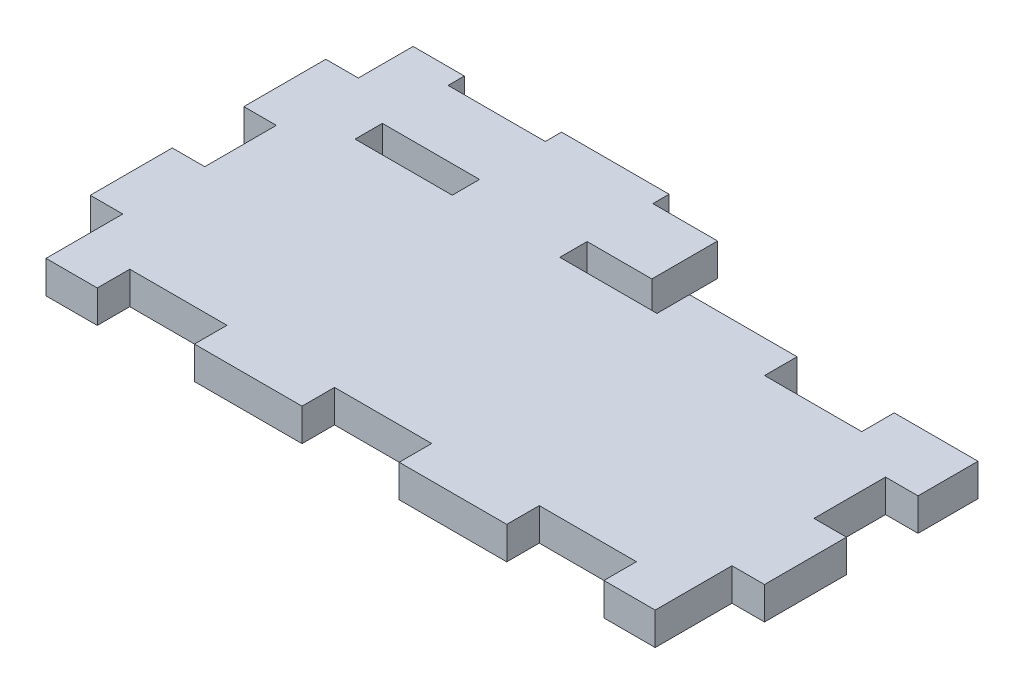
SolidWorks part; units mm, degrees
ref_plane "Front Plane" through (0, 0, 0) normal (0, 0, 1) x (1, 0, 0)
ref_plane "Top Plane" through (0, 0, 0) normal (0, 1, 0) x (1, 0, 0)
ref_plane "Right Plane" through (0, 0, 0) normal (1, 0, 0) x (0, 0, -1)
sketch "Sketch1" plane through (0, 0, 0) normal (0, 1, 0) x (1, 0, 0)
  line L1 (0, 0) -> (65.35, 0)
  line L2 (0, 0) -> (0, 35.35)
  line L3 (0, 35.35) -> (65.35, 35.35)
  line L4 (65.35, 0) -> (65.35, 35.35)
  dimension "D1" = 65.35
  dimension "D2" = 35.35
extrude "Boss-Extrude1" add sketch "Sketch1" along normal blind 3.175
sketch "Sketch2" plane through (0, 0, 0) normal (0, -1, 0) x (1, 0, 0)
  line L0 (65.35, -35.35) -> (0, -35.35) construction
  line L1 (65.35, -35.35) -> (37.175, -35.35)
  line L2 (65.35, -35.35) -> (65.35, -27.85)
  line L3 (65.35, -27.85) -> (37.175, -27.85)
  line L4 (37.175, -35.35) -> (37.175, -27.85)
  line L5 (65.35, 0) -> (65.35, -35.35) construction
  dimension "D1" = 7.5
  dimension "D2" = 28.175
extrude "Cut-Extrude1" cut sketch "Sketch2" against normal through all
sketch "Sketch3" plane through (0, 0, 0) normal (0, -1, 0) x (1, 0, 0)
  line L0 (0, 0) -> (65.35, 0) construction
  line L1 (62.175, -7.5) -> (65.35, -7.5)
  line L2 (62.175, -7.5) -> (62.175, 0)
  line L3 (62.175, 0) -> (65.35, 0)
  line L4 (65.35, -7.5) -> (65.35, 0)
  line L5 (0, -35.35) -> (0, 0) construction
  line L6 (57.675, -3.175) -> (47.675, -3.175)
  line L7 (57.675, -3.175) -> (57.675, 0)
  line L8 (57.675, 0) -> (47.675, 0)
  line L9 (47.675, -3.175) -> (47.675, 0)
  line L10 (37.675, -3.175) -> (27.675, -3.175)
  line L11 (37.675, -3.175) -> (37.675, 0)
  line L12 (37.675, 0) -> (27.675, 0)
  line L13 (27.675, -3.175) -> (27.675, 0)
  line L14 (17.675, -3.175) -> (7.675, -3.175)
  line L15 (17.675, -3.175) -> (17.675, 0)
  line L16 (17.675, 0) -> (7.675, 0)
  line L17 (7.675, -3.175) -> (7.675, 0)
  line L18 (3.175, -7.5) -> (0, -7.5)
  line L19 (3.175, -7.5) -> (3.175, 0)
  line L20 (3.175, 0) -> (0, 0)
  line L21 (0, -7.5) -> (0, 0)
  line L22 (37.175, -35.35) -> (0, -35.35) construction
  line L23 (3.175, -15) -> (0, -15)
  line L24 (3.175, -15) -> (3.175, -22.5)
  line L25 (3.175, -22.5) -> (0, -22.5)
  line L26 (0, -15) -> (0, -22.5)
  line L27 (3.175, -30) -> (0, -30)
  line L28 (3.175, -30) -> (3.175, -35.35)
  line L29 (3.175, -35.35) -> (0, -35.35)
  line L30 (0, -30) -> (0, -35.35)
  line L31 (7.675, -33.7625) -> (17.675, -33.7625)
  line L32 (7.675, -33.7625) -> (7.675, -35.35)
  line L33 (7.675, -35.35) -> (17.675, -35.35)
  line L34 (17.675, -33.7625) -> (17.675, -35.35)
  line L35 (65.35, -27.85) -> (37.175, -27.85) construction
  line L36 (17.675, -27.85) -> (7.675, -27.85)
  line L37 (17.675, -27.85) -> (17.675, -24.675)
  line L38 (17.675, -24.675) -> (7.675, -24.675)
  line L39 (7.675, -27.85) -> (7.675, -24.675)
  line L40 (27.675, -27.85) -> (37.675, -27.85)
  line L41 (27.675, -27.85) -> (27.675, -24.675)
  line L42 (27.675, -24.675) -> (37.675, -24.675)
  line L43 (37.675, -27.85) -> (37.675, -24.675)
  line L44 (34, -27.85) -> (37.175, -27.85)
  line L45 (34, -27.85) -> (34, -33.7625)
  line L46 (34, -33.7625) -> (37.175, -33.7625)
  line L47 (37.175, -27.85) -> (37.175, -33.7625)
  line L48 (27.675, -33.7625) -> (37.175, -33.7625)
  line L49 (27.675, -33.7625) -> (27.675, -35.35)
  line L50 (27.675, -35.35) -> (37.175, -35.35)
  line L51 (37.175, -33.7625) -> (37.175, -35.35)
  line L52 (47.675, -24.675) -> (57.675, -24.675)
  line L53 (47.675, -24.675) -> (47.675, -27.85)
  line L54 (47.675, -27.85) -> (57.675, -27.85)
  line L55 (57.675, -24.675) -> (57.675, -27.85)
  line L56 (65.35, 0) -> (65.35, -27.85) construction
  line L57 (62.175, -22.5) -> (65.35, -22.5)
  line L58 (62.175, -22.5) -> (62.175, -15)
  line L59 (62.175, -15) -> (65.35, -15)
  line L60 (65.35, -22.5) -> (65.35, -15)
  line L62 (37.175, -27.85) -> (37.175, -35.35) construction
  line M40 (37.175, -35.35) -> (37.175, -27.85)
  line M41 (37.175, -27.85) -> (65.35, -27.85)
  line M42 (65.35, -27.85) -> (65.35, 0)
  line M43 (65.35, 0) -> (0, 0)
  line M44 (0, 0) -> (0, -35.35)
  line M45 (0, -35.35) -> (37.175, -35.35)
  dimension "D1" = 10
  dimension "D2" = 10
  dimension "D3" = 10
  dimension "D4" = 10
  dimension "D5" = 10
  dimension "D6" = 4.5
  dimension "D7" = 3.175
  dimension "D8" = 7.5
  dimension "D9" = 7.5
  dimension "D10" = 5.35
  dimension "D11" = 7.5
  dimension "D12" = 7.5
  dimension "D13" = 5.9125
  dimension "D14" = 1.5875
extrude "Cut-Extrude2" cut sketch "Sketch3" against normal blind 3.175 contours L9 L6 L7 M43 | L2 L1 M42 M43 | L59 L58 L57 M42 | L55 L52 L53 M41 | L43 L42 L41 L40 M41 | L45 L46 L40 M40 | L48 L49 L46 M45 M40 | L39 L36 L37 L38 | L28 L27 M44 M45 | L25 L24 L23 M44 | L18 L19 M43 M44 | L17 L14 L15 M43 | L13 L10 L11 M43 | L33 L34 L31 L32 region at (63.7625, 0, -3.75) region at (63.7625, 0, -18.75) region at (52.675, 0, -1.5875) region at (32.675, 0, -1.5875) region at (52.675, 0, -26.2625) region at (12.675, 0, -1.5875) region at (32.675, 0, -26.2625) region at (35.5875, 0, -30.8063) region at (1.5875, 0, -3.75) region at (32.425, 0, -34.5563) region at (1.5875, 0, -18.75) region at (1.5875, 0, -32.675) region at (12.675, 0, -26.2625)
sketch "Sketch6" plane through (0, 3.175, 0) normal (0, 1, 0) x (1, 0, 0)
  line L60 (17.421, 27.596) -> (7.929, 27.596)
  line L61 (7.929, 27.596) -> (7.929, 24.929)
  line L62 (7.929, 24.929) -> (17.421, 24.929)
  line L63 (17.421, 24.929) -> (17.421, 27.596)
  line L64 (17.421, 27.596) -> (7.929, 27.596)
  line L65 (7.929, 27.596) -> (7.929, 24.929)
  line L66 (7.929, 24.929) -> (17.421, 24.929)
  line L67 (17.421, 24.929) -> (17.421, 27.596)
  line L92 (7.929, -0.254) -> (7.929, 2.921)
  line L93 (7.929, 2.921) -> (17.421, 2.921)
  line L94 (17.421, 2.921) -> (17.421, -0.254)
  line L95 (17.421, -0.254) -> (27.929, -0.254)
  line L96 (27.929, -0.254) -> (27.929, 2.921)
  line L97 (27.929, 2.921) -> (37.421, 2.921)
  line L98 (37.421, 2.921) -> (37.421, -0.254)
  line L99 (37.421, -0.254) -> (47.929, -0.254)
  line L100 (47.929, -0.254) -> (47.929, 2.921)
  line L101 (47.929, 2.921) -> (57.421, 2.921)
  line L102 (57.421, 2.921) -> (57.421, -0.254)
  line L103 (57.421, -0.254) -> (62.429, -0.254)
  line L104 (62.429, -0.254) -> (62.429, 7.246)
  line L105 (62.429, 7.246) -> (65.604, 7.246)
  line L106 (65.604, 7.246) -> (65.604, 15.254)
  line L107 (65.604, 15.254) -> (62.429, 15.254)
  line L108 (62.429, 15.254) -> (62.429, 22.246)
  line L109 (62.429, 22.246) -> (65.604, 22.246)
  line L110 (65.604, 22.246) -> (65.604, 28.104)
  line L111 (65.604, 28.104) -> (57.421, 28.104)
  line L112 (57.421, 28.104) -> (57.421, 24.929)
  line L113 (57.421, 24.929) -> (47.929, 24.929)
  line L114 (47.929, 24.929) -> (47.929, 28.104)
  line L115 (47.929, 28.104) -> (37.421, 28.104)
  line L116 (37.421, 28.104) -> (37.421, 24.929)
  line L117 (37.421, 24.929) -> (27.929, 24.929)
  line L118 (27.929, 24.929) -> (27.929, 27.596)
  line L119 (27.929, 27.596) -> (34.254, 27.596)
  line L120 (34.254, 27.596) -> (34.254, 34.0165)
  line L121 (34.254, 34.0165) -> (27.929, 34.0165)
  line L122 (27.929, 34.0165) -> (27.929, 35.604)
  line L123 (27.929, 35.604) -> (17.421, 35.604)
  line L124 (17.421, 35.604) -> (17.421, 34.0165)
  line L125 (17.421, 34.0165) -> (7.929, 34.0165)
  line L126 (7.929, 34.0165) -> (7.929, 35.604)
  line L127 (7.929, 35.604) -> (2.921, 35.604)
  line L128 (2.921, 35.604) -> (2.921, 30.254)
  line L129 (2.921, 30.254) -> (-0.254, 30.254)
  line L130 (-0.254, 30.254) -> (-0.254, 22.246)
  line L131 (-0.254, 22.246) -> (2.921, 22.246)
  line L132 (2.921, 22.246) -> (2.921, 15.254)
  line L133 (2.921, 15.254) -> (-0.254, 15.254)
  line L134 (-0.254, 15.254) -> (-0.254, 7.246)
  line L135 (-0.254, 7.246) -> (2.921, 7.246)
  line L136 (2.921, 7.246) -> (2.921, -0.254)
  line L137 (2.921, -0.254) -> (7.929, -0.254)
  line L138 (7.929, -0.254) -> (7.929, 2.921)
  line L139 (7.929, 2.921) -> (17.421, 2.921)
  line L140 (17.421, 2.921) -> (17.421, -0.254)
  line L141 (17.421, -0.254) -> (27.929, -0.254)
  line L142 (27.929, -0.254) -> (27.929, 2.921)
  line L143 (27.929, 2.921) -> (37.421, 2.921)
  line L144 (37.421, 2.921) -> (37.421, -0.254)
  line L145 (37.421, -0.254) -> (47.929, -0.254)
  line L146 (47.929, -0.254) -> (47.929, 2.921)
  line L147 (47.929, 2.921) -> (57.421, 2.921)
  line L148 (57.421, 2.921) -> (57.421, -0.254)
  line L149 (57.421, -0.254) -> (62.429, -0.254)
  line L150 (62.429, -0.254) -> (62.429, 7.246)
  line L151 (62.429, 7.246) -> (65.604, 7.246)
  line L152 (65.604, 7.246) -> (65.604, 15.254)
  line L153 (65.604, 15.254) -> (62.429, 15.254)
  line L154 (62.429, 15.254) -> (62.429, 22.246)
  line L155 (62.429, 22.246) -> (65.604, 22.246)
  line L156 (65.604, 22.246) -> (65.604, 28.104)
  line L157 (65.604, 28.104) -> (57.421, 28.104)
  line L158 (57.421, 28.104) -> (57.421, 24.929)
  line L159 (57.421, 24.929) -> (47.929, 24.929)
  line L160 (47.929, 24.929) -> (47.929, 28.104)
  line L161 (47.929, 28.104) -> (37.421, 28.104)
  line L162 (37.421, 28.104) -> (37.421, 24.929)
  line L163 (37.421, 24.929) -> (27.929, 24.929)
  line L164 (27.929, 24.929) -> (27.929, 27.596)
  line L165 (27.929, 27.596) -> (34.254, 27.596)
  line L166 (34.254, 27.596) -> (34.254, 34.0165)
  line L167 (34.254, 34.0165) -> (27.929, 34.0165)
  line L168 (27.929, 34.0165) -> (27.929, 35.604)
  line L169 (27.929, 35.604) -> (17.421, 35.604)
  line L170 (17.421, 35.604) -> (17.421, 34.0165)
  line L171 (17.421, 34.0165) -> (7.929, 34.0165)
  line L172 (7.929, 34.0165) -> (7.929, 35.604)
  line L173 (7.929, 35.604) -> (2.921, 35.604)
  line L174 (2.921, 35.604) -> (2.921, 30.254)
  line L175 (2.921, 30.254) -> (-0.254, 30.254)
  line L176 (-0.254, 30.254) -> (-0.254, 22.246)
  line L177 (-0.254, 22.246) -> (2.921, 22.246)
  line L178 (2.921, 22.246) -> (2.921, 15.254)
  line L179 (2.921, 15.254) -> (-0.254, 15.254)
  line L180 (-0.254, 15.254) -> (-0.254, 7.246)
  line L181 (-0.254, 7.246) -> (2.921, 7.246)
  line L182 (2.921, 7.246) -> (2.921, -0.254)
  line L183 (2.921, -0.254) -> (7.929, -0.254)
  dimension "D1" = 0.254
  dimension "D2" = 0.254
extrude "Boss-Extrude2" add sketch "Sketch6" against normal blind 3.175
